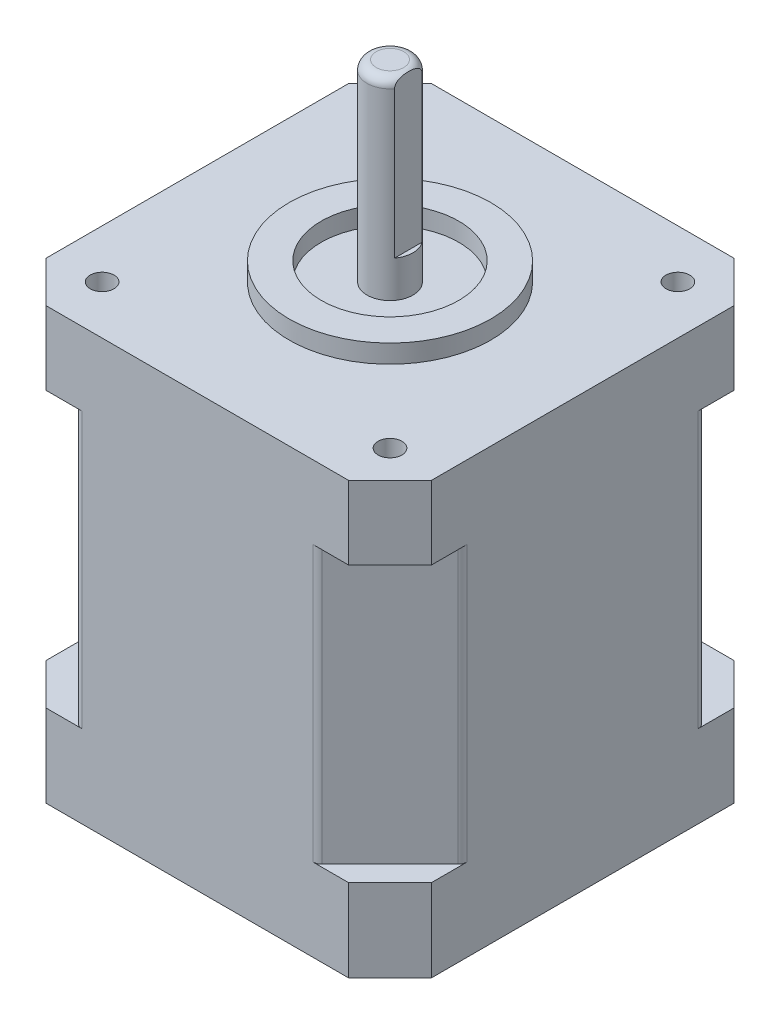
SolidWorks part; units mm, degrees
ref_plane "Alzado" through (0, 0, 0) normal (0, 0, 1) x (1, 0, 0)
ref_plane "Planta" through (0, 0, 0) normal (0, 1, 0) x (1, 0, 0)
ref_plane "Vista lateral" through (0, 0, 0) normal (1, 0, 0) x (0, 0, -1)
sketch "Croquis1" plane through (0, 0, 0) normal (0, 1, 0) x (1, 0, 0)
  line L0 (-16.5, 21) -> (-21, 16.5)
  line L1 (16.5, -21) -> (-16.5, -21)
  line L2 (21, -16.5) -> (21, 16.5)
  line L3 (16.5, 21) -> (8.5, 21)
  line L4 (-21, -16.5) -> (-21, 16.5)
  line L5 (21, -21) -> (-21, 21) construction
  line L6 (21, 21) -> (-21, -21) construction
  line L7 (16.5, 21) -> (21, 16.5)
  line L8 (16.5, -21) -> (21, -16.5)
  line L9 (-21, -16.5) -> (-16.5, -21)
  line L10 (-8.5, 21) -> (-16.5, 21)
  line L12 (-8.5, 21) -> (-8.5, 25)
  line L13 (-8.5, 25) -> (8.5, 25)
  line L14 (8.5, 21) -> (8.5, 25)
  point P0 (0, 0)
  dimension "D1" = 42
  dimension "D2" = 42
  dimension "D3" = 4.5
  dimension "D4" = 4.5
  dimension "D5" = 4.5
  dimension "D6" = 4.5
  dimension "D7" = 4.5
  dimension "D8" = 4.5
  dimension "D9" = 8
  dimension "D10" = 8
  dimension "D11" = 4
extrude "Saliente-Extruir1" add sketch "Croquis1" along normal blind 9
sketch "Croquis2" plane through (0, 0, 0) normal (0, 1, 0) x (1, 0, 0)
  line L0 (13, 21) -> (21, 13)
  line L1 (13, -21) -> (-13, -21)
  line L2 (21, -13) -> (21, 13)
  line L3 (13, 21) -> (-13, 21)
  line L4 (-21, -13) -> (-21, 13)
  line L5 (21, -21) -> (-21, 21) construction
  line L6 (21, 21) -> (-21, -21) construction
  line L7 (-21, 13) -> (-13, 21)
  line L8 (-13, -21) -> (-21, -13)
  line L9 (13, -21) -> (21, -13)
  point P0 (0, 0)
  dimension "D1" = 42
  dimension "D2" = 42
  dimension "D3" = 8
  dimension "D4" = 8
  dimension "D5" = 8
  dimension "D6" = 8
  dimension "D7" = 8
  dimension "D8" = 8
extrude "Saliente-Extruir2" add sketch "Croquis2" along normal blind 30 from offset 9
fillet "Redondeo3" radius 1 8 edges at (-13, 24, 21) (-21, 24, 13) (-21, 24, -13) (-13, 24, -21) (13, 24, -21) (21, 24, -13) (21, 24, 13) (13, 24, 21)
sketch "Croquis3" plane through (0, 0, 0) normal (0, 1, 0) x (1, 0, 0)
  line L0 (-16.5, 21) -> (-21, 16.5)
  line L1 (16.5, -21) -> (-16.5, -21)
  line L2 (21, -16.5) -> (21, 16.5)
  line L3 (16.5, 21) -> (-16.5, 21)
  line L4 (-21, -16.5) -> (-21, 16.5)
  line L5 (21, -21) -> (-21, 21) construction
  line L6 (21, 21) -> (-21, -21) construction
  line L7 (-21, -16.5) -> (-16.5, -21)
  line L8 (16.5, 21) -> (21, 16.5)
  line L9 (21, -16.5) -> (16.5, -21)
  point P0 (0, 0)
  dimension "D1" = 42
  dimension "D2" = 42
extrude "Saliente-Extruir3" add sketch "Croquis3" along normal blind 8 from offset 39
sketch "Croquis4" plane through (0, 0, 0) normal (0, 1, 0) x (1, 0, 0)
  line L0 (-21, 16.5) -> (-21, -16.5) construction
  line L1 (21, -16.5) -> (21, 16.5) construction
  line L2 (16.5, 21) -> (-16.5, 21) construction
  line L3 (-16.5, -21) -> (16.5, -21) construction
  circle A0 centre (-15.7, 15.7) radius 1.3
  circle A1 centre (15.7, 15.7) radius 1.3
  circle A2 centre (15.7, -15.7) radius 1.3
  circle A3 centre (-15.7, -15.7) radius 1.3
  dimension "D1" = 2.6
  dimension "D2" = 2.6
  dimension "D3" = 2.6
  dimension "D4" = 2.6
  dimension "D5" = 5.3
  dimension "D6" = 5.3
  dimension "D7" = 5.3
  dimension "D8" = 5.3
  dimension "D9" = 5.3
  dimension "D10" = 5.3
  dimension "D11" = 5.3
  dimension "D12" = 5.3
extrude "Cortar-Extruir1" cut sketch "Croquis4" against normal blind 5 from offset 47
sketch "Croquis5" plane through (0, 0, 0) normal (0, 1, 0) x (1, 0, 0)
  circle A0 centre (0, 0) radius 11
  circle A1 centre (0, 0) radius 7.5
  dimension "D1" = 22
  dimension "D2" = 15
extrude "Saliente-Extruir4" add sketch "Croquis5" along normal blind 2 from offset 47
sketch "Croquis6" plane through (0, 0, 0) normal (0, 1, 0) x (1, 0, 0)
  circle A0 centre (0, 0) radius 2.5
  dimension "D1" = 5
extrude "Saliente-Extruir5" add sketch "Croquis6" along normal blind 21 from offset 47
sketch "Croquis7" plane through (0, 0, 0) normal (0, 1, 0) x (1, 0, 0)
  line L1 (2, -1.5) -> (2, 1.5)
  circle A1 centre (0, 0) radius 2.5 construction
  arc A2 (2, -1.5) -> (2, 1.5) centre (0, 0) ccw
extrude "Cortar-Extruir2" cut sketch "Croquis7" against normal blind 17 from offset 68
fillet "Redondeo4" radius 1 1 edges at (-2.5, 68, 0)
